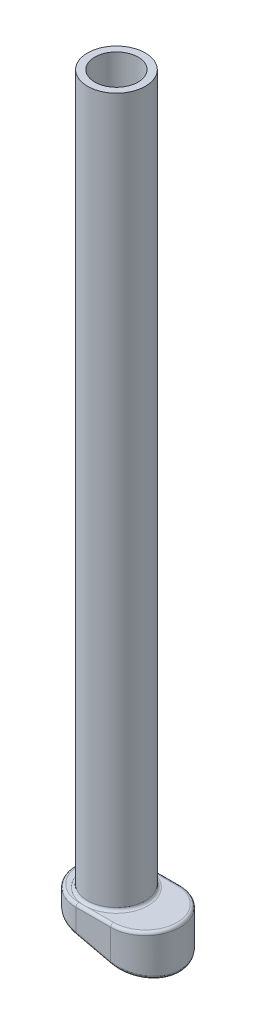
SolidWorks part; units mm, degrees
ref_plane "前视基准面" through (0, 0, 0) normal (0, 0, 1) x (1, 0, 0)
ref_plane "上视基准面" through (0, 0, 0) normal (0, 1, 0) x (1, 0, 0)
ref_plane "右视基准面" through (0, 0, 0) normal (1, 0, 0) x (0, 0, -1)
sketch "草图1" plane through (0, 0, 0) normal (0, 1, 0) x (1, 0, 0)
  circle A0 centre (0, 0) radius 10
  circle A1 centre (0, 0) radius 7.5
  dimension "D1" = 20
  dimension "D2" = 15
extrude "凸台-拉伸1" add sketch "草图1" along normal blind 250
sketch "草图2" plane through (0, 0, 0) normal (0, 1, 0) x (1, 0, 0)
  line L0 (10, 0) -> (-2, 0) construction
  line L1 (10, -12) -> (-2, -12)
  line L2 (10, 12) -> (-2, 12)
  arc A0 (10, -12) -> (10, 12) centre (10, 0) ccw
  arc A1 (-2, 12) -> (-2, -12) centre (-2, 0) ccw
  point P2 (4, 0)
  point P8 (4.0933, 0)
  point P9 (-2.1598, 0)
  point P10 (3.5249, 0)
  dimension "D2" = 12
  dimension "D1" = 4
  dimension "D3" = 2
extrude "凸台-拉伸2" add sketch "草图2" along normal blind 5 and the other way blind 10
sketch "草图4" plane through (0, 0, 0) normal (0, 0, 1) x (1, 0, 0)
  line L0 (-14, -10) -> (22, -10) construction
  line L1 (10, -10) -> (22, -10) construction
  line L2 (22, -10) -> (-14, -1.6887) construction
  line L3 (-14, 5) -> (-14, -10) construction
  line L4 (-14, -1.6887) -> (-14, -10)
  line L5 (-14, -10) -> (22, -10)
  line L6 (22, -10) -> (-14, -1.6887)
  dimension "D1" = 13
extrude "切除-拉伸1" cut sketch "草图4" against normal through all both and the other way through all
fillet "圆角1" radius 1 9 edges at (4, 5, 12) (-14, 5, 0) (4, 5, -12) (4, -5.8444, 12) (22, -10, 0) (4, -5.8444, -12) (0, 5, 10) (22, 5, 0) (-14, -1.6887, 0)
sketch "草图5" plane through (-1.0786, -4.6719, 0) normal (-0.225, -0.9744, 0) x (0.9744, -0.225, 0)
  line L0 (0, 0) -> (-12.4659, 0) construction
  line L2 (5.3923, -6) -> (5.3923, 6) construction
  line L3 (5.3923, 6) -> (-5, 12) construction
  line L4 (-5, 12) -> (-15.3923, 6) construction
  line L5 (-15.3923, 6) -> (-15.3923, -6) construction
  line L6 (-15.3923, -6) -> (-5, -12) construction
  line L7 (-5, -12) -> (5.3923, -6) construction
  circle A0 centre (-5, 0) radius 4
  circle A1 centre (-5, 0) radius 10.3923 construction
  circle A2 centre (5.3923, 6) radius 2
  circle A3 centre (5.3923, -6) radius 2
  ellipse E0 centre (-1.1765, 0) end of major axis (-12.4659, 0) minor radius 11 (-1.1765, 11) -> (-1.1765, -11) ccw construction
  dimension "D1" = 8
  dimension "D4" = 4
  dimension "D5" = 4
  dimension "D2" = 5
  dimension "D3" = 12
extrude "切除-拉伸2" cut sketch "草图5" against normal blind 5
